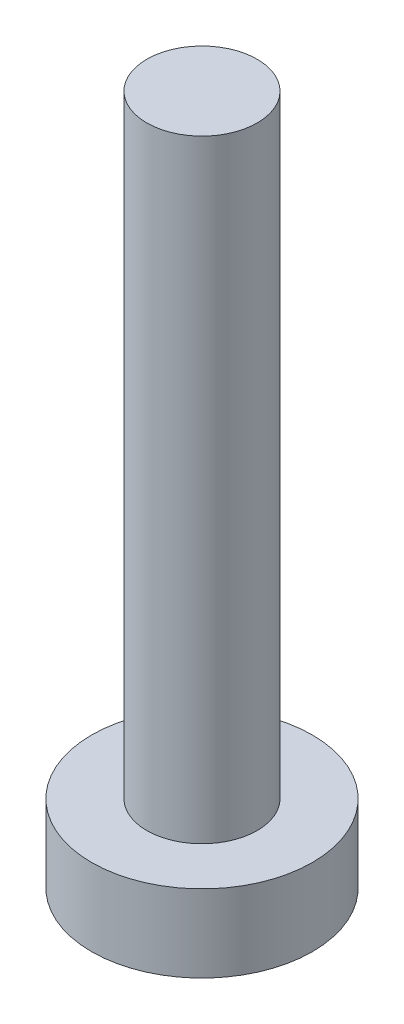
SolidWorks part; units mm, degrees
ref_plane "Front Plane" through (0, 0, 0) normal (0, 0, 1) x (1, 0, 0)
ref_plane "Top Plane" through (0, 0, 0) normal (0, 1, 0) x (1, 0, 0)
ref_plane "Right Plane" through (0, 0, 0) normal (1, 0, 0) x (0, 0, -1)
sketch "Sketch1" plane through (0, 0, 0) normal (0, 1, 0) x (1, 0, 0)
  circle A0 centre (0, 0) radius 2
  circle A1 centre (0, 0) radius 4
  dimension "D1" = 8
  dimension "D2" = 4
extrude "Boss-Extrude1" add sketch "Sketch1" along normal blind 2.8 contours A0 | A1 A0 region at (0, 0, 0) region at (-3.8869, 0, 0)
extrude "Boss-Extrude2" add sketch "Sketch1<3>" along normal blind 22.2 from surface contours A0 region at (0, 0, 0) starting at face at (0, 2.8, 4)
sketch "Sketch1<3>" plane through (0, 0, 0) normal (0, 1, 0) x (1, 0, 0) same geometry as "Sketch1"
